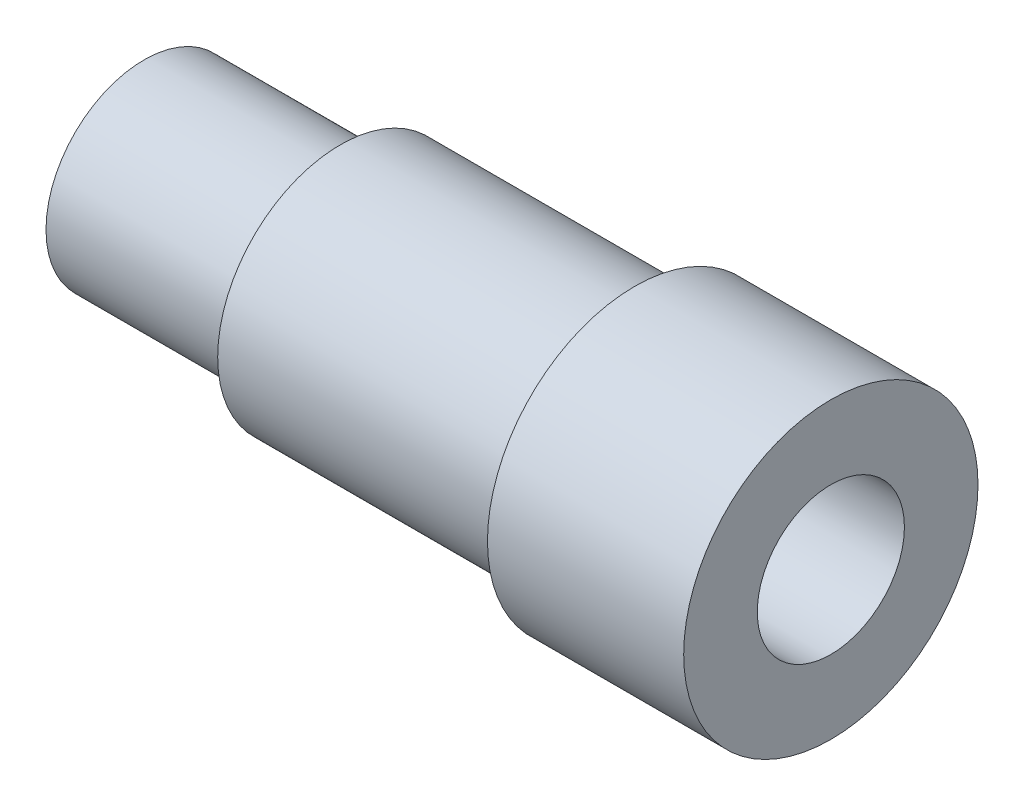
SolidWorks part; units mm, degrees
ref_plane "Front Plane" through (0, 0, 0) normal (1, 0, 0) x (0, 1, 0)
ref_plane "Top Plane" through (0, 0, 0) normal (0, 0, 1) x (0, 1, 0)
ref_plane "Right Plane" through (0, 0, 0) normal (0, 1, 0) x (-1, 0, 0)
sketch "Sketch2" plane through (0, 0, 0) normal (1, 0, 0) x (0, 1, 0)
  circle A0 centre (0, 0) radius 7.9375
  circle A1 centre (0, 0) radius 4.7625
  dimension "D1" = 15.875
  dimension "D2" = 9.525
extrude "Boss-Extrude1" add sketch "Sketch2" along normal blind 44.45
sketch "Sketch3" plane through (44.45, 0, 0) normal (1, 0, 0) x (0, 1, 0)
  circle A0 centre (0, 0) radius 7.9375
  circle A1 centre (0, 0) radius 9.525
  dimension "D1" = 19.05
  dimension "D2" = 15.875
extrude "Boss-Extrude2" add sketch "Sketch3" against normal blind 12.7
sketch "Sketch4" plane through (0, 0, 0) normal (-1, 0, 0) x (0, -1, 0)
  circle A0 centre (0, 0) radius 7.9375
  circle A1 centre (0, 0) radius 6.35
  dimension "D1" = 15.875
  dimension "D2" = 12.7
extrude "Cut-Extrude1" cut sketch "Sketch4" against normal blind 12.7
